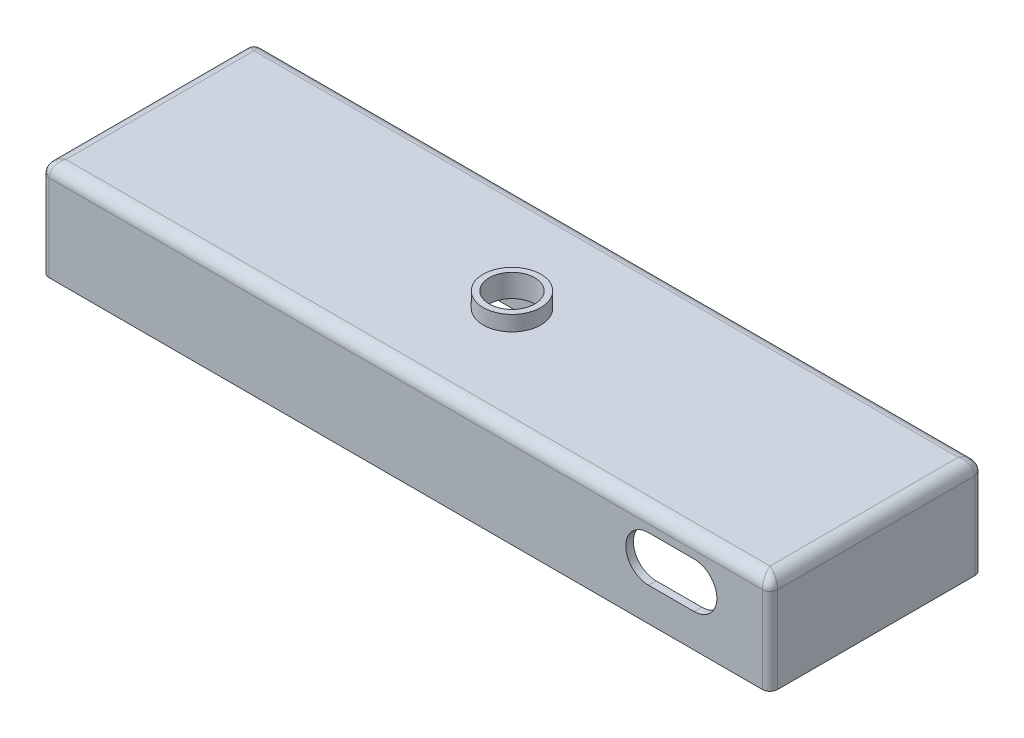
SolidWorks part; units mm, degrees
material "Gray Cast Iron (SN)"
ref_plane "Front Plane" through (0, 0, 0) normal (0, 0, 1) x (1, 0, 0)
ref_plane "Top Plane" through (0, 0, 0) normal (0, 1, 0) x (1, 0, 0)
ref_plane "Right Plane" through (0, 0, 0) normal (1, 0, 0) x (0, 0, -1)
sketch "Sketch1" plane through (0, 0, 0) normal (0, 0, 1) x (1, 0, 0)
  line L1 (-240, 0) -> (240, 0)
  line L2 (-240, 0) -> (-240, 65)
  line L3 (-240, 65) -> (240, 65)
  line L4 (240, 0) -> (240, 65)
  dimension "D1" = 480
  dimension "D2" = 65
extrude "Boss-Extrude1" add sketch "Sketch1" along normal blind 140
shell "Shell1" thickness 5 removed face at (0, 0, 70)
fillet "Fillet1" radius 5 4 edges at (-240, 32.5, 0) (240, 32.5, 140) (240, 32.5, 0) (-240, 32.5, 140)
fillet "Fillet2" radius 8 8 edges at (238.5355, 65, 1.4645) (240, 65, 70) (238.5355, 65, 138.5355) (0, 65, 140) (-238.5355, 65, 138.5355) (-240, 65, 70) (-238.5355, 65, 1.4645) (0, 65, 0)
sketch "Sketch2" plane through (0, 65, 0) normal (0, 1, 0) x (1, 0, 0)
  line L0 (0, 0) -> (0, -140) construction
  line L1 (235, -140) -> (-235, -140) construction
  circle A0 centre (0, -70) radius 15
  circle A1 centre (0, -70) radius 19
  dimension "D1" = 38
  dimension "D2" = 30
extrude "Boss-Extrude2" add sketch "Sketch2" along normal blind 10
sketch "Sketch3" plane through (0, 65, 0) normal (0, 1, 0) x (1, 0, 0)
  circle A1 centre (0, -70) radius 15
  circle A2 centre (0, -70) radius 15
  dimension "D1" = 0
extrude "Cut-Extrude1" cut sketch "Sketch3" against normal up to next
sketch "Sketch4" plane through (0, 0, 140) normal (0, 0, 1) x (1, 0, 0)
  line L0 (160, 37) -> (190, 37) construction
  line L1 (160, 52) -> (190, 52)
  line L2 (160, 22) -> (190, 22)
  line L3 (-232, 65) -> (232, 65) construction
  line L4 (175, 65) -> (175, 0) construction
  line L5 (-235, 0) -> (235, 0) construction
  line L6 (240, 57) -> (240, 0) construction
  arc A0 (160, 52) -> (160, 22) centre (160, 37) ccw
  arc A1 (190, 22) -> (190, 52) centre (190, 37) ccw
  point P2 (175, 37)
  dimension "D1" = 15
  dimension "D2" = 30
  dimension "D3" = 65
  dimension "D4" = 28
extrude "Cut-Extrude2" cut sketch "Sketch4" against normal up to next
